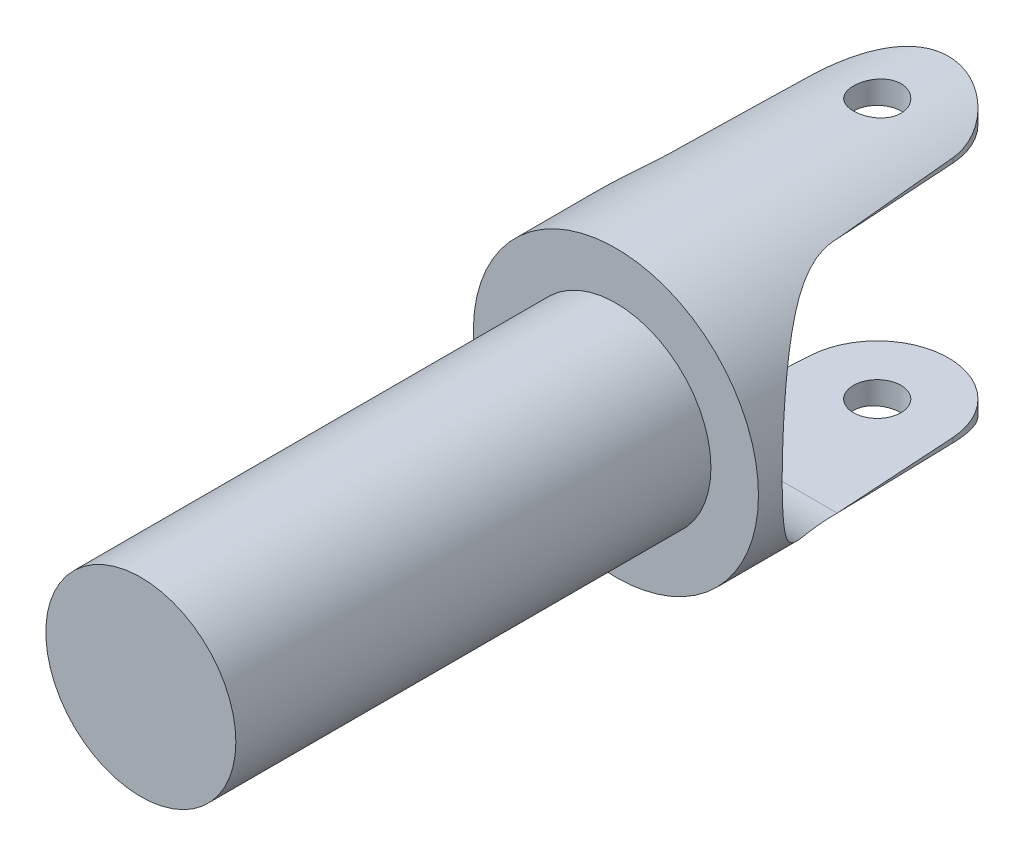
SolidWorks part; units mm, degrees
ref_plane "Front Plane" through (0, 0, 0) normal (0, 0, 1) x (1, 0, 0)
ref_plane "Top Plane" through (0, 0, 0) normal (0, 1, 0) x (1, 0, 0)
ref_plane "Right Plane" through (0, 0, 0) normal (1, 0, 0) x (0, 0, -1)
sketch "Base Sketch" plane through (0, 0, 0) normal (0, 0, 1) x (1, 0, 0)
  circle A0 centre (0, 0) radius 30
  dimension "D1" = 60
extrude "Base Extrude" add sketch "Base Sketch" along normal blind 30
sketch "Pin Sketch" plane through (0, 0, 30) normal (0, 0, 1) x (1, 0, 0)
  circle A0 centre (0, 0) radius 20
  dimension "D1" = 40
extrude "Pin Extrude" add sketch "Pin Sketch" along normal blind 100
sketch "Side Cut Sketch" plane through (0, 0, 0) normal (1, 0, 0) x (0, 0, -1)
  circle A0 centre (0, 0) radius 25
  dimension "D1" = 50
extrude "Side Cut" cut sketch "Side Cut Sketch" against normal up to surface and the other way up to surface up to face at (30, 0, 30) other way up to face at (30, 0, 30)
ref_plane "Wing Cutoff Plane" through (0, 25, 0) normal (0, 1, 0) x (1, 0, 0)
sketch "Wing Sketch" plane through (0, 25, 0) normal (0, 1, 0) x (1, 0, 0)
  line L0 (16.5831, 0) -> (-16.5831, 0) construction
  line L1 (-16.5831, 0) -> (-14.9711, 25.9307)
  line L2 (16.5831, 0) -> (14.9711, 25.9307)
  line L3 (-14.9711, 25.9307) -> (14.9711, 25.9307) construction
  line L4 (-16.5831, 0) -> (16.5831, 0)
  arc A0 (14.9711, 25.9307) -> (-14.9711, 25.9307) centre (0, 25) ccw
  dimension "D1" = 30
  dimension "D2" = 25
extrude "Wing Extrude" add sketch "Wing Sketch" along normal up to surface (0.9974 mm away) up to face at (30, 0, 30)
mirror "Wing Mirror" about plane through (0, 0, 0) normal (0, 1, 0) of "Wing Extrude"
sketch "Pin Hole Sketch" plane through (0, 25, 0) normal (0, -1, 0) x (1, 0, 0)
  circle A0 centre (0, -25) radius 5
  arc A1 (-14.9711, -25.9307) -> (14.9711, -25.9307) centre (0, -25) ccw construction
  dimension "D1" = 10
extrude "Pin Hole Cut" cut sketch "Pin Hole Sketch" along normal through all both and the other way through all
